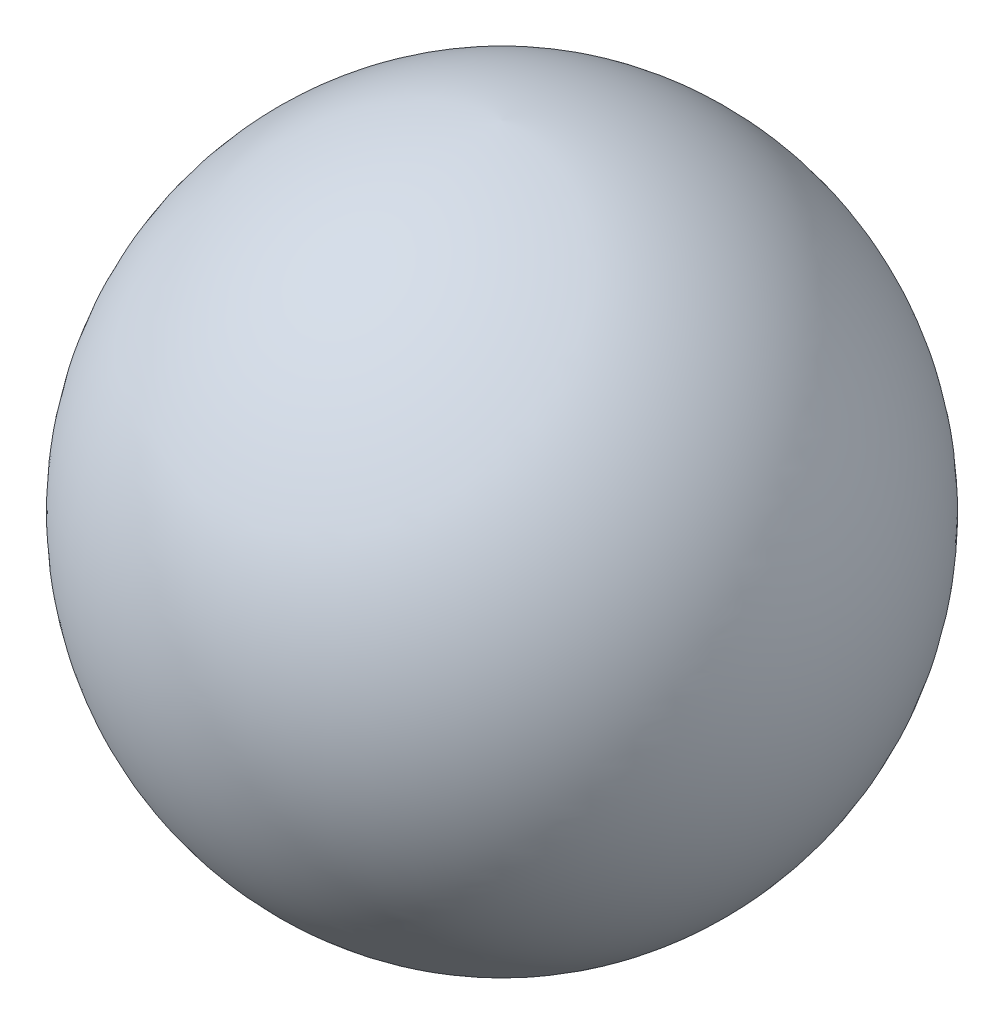
SolidWorks part; units mm, degrees
material "Alumina"
ref_plane "Front Plane" through (0, 0, 0) normal (0, 0, 1) x (1, 0, 0)
ref_plane "Top Plane" through (0, 0, 0) normal (0, 1, 0) x (1, 0, 0)
ref_plane "Right Plane" through (0, 0, 0) normal (1, 0, 0) x (0, 0, -1)
ref_axis "X-axis" through (-88.99, 0, 0) along (1, 0, 0)
ref_axis "Y-axis" through (0, 55, 0) along (0, -1, 0)
ref_axis "Z-axis" through (0, 0, -88.99) along (0, 0, 1)
sketch "Sketch1" plane through (0, 0, 0) normal (0, 0, 1) x (1, 0, 0)
  line L0 (0, 0) -> (0, 0.7191)
  arc A0 (0, 0.7191) -> (0, 0) centre (0.0184, 0.3595) ccw
  dimension "D1" = 0.36
revolve "Revolve1" add sketch "Sketch1" angle 360 about L0
